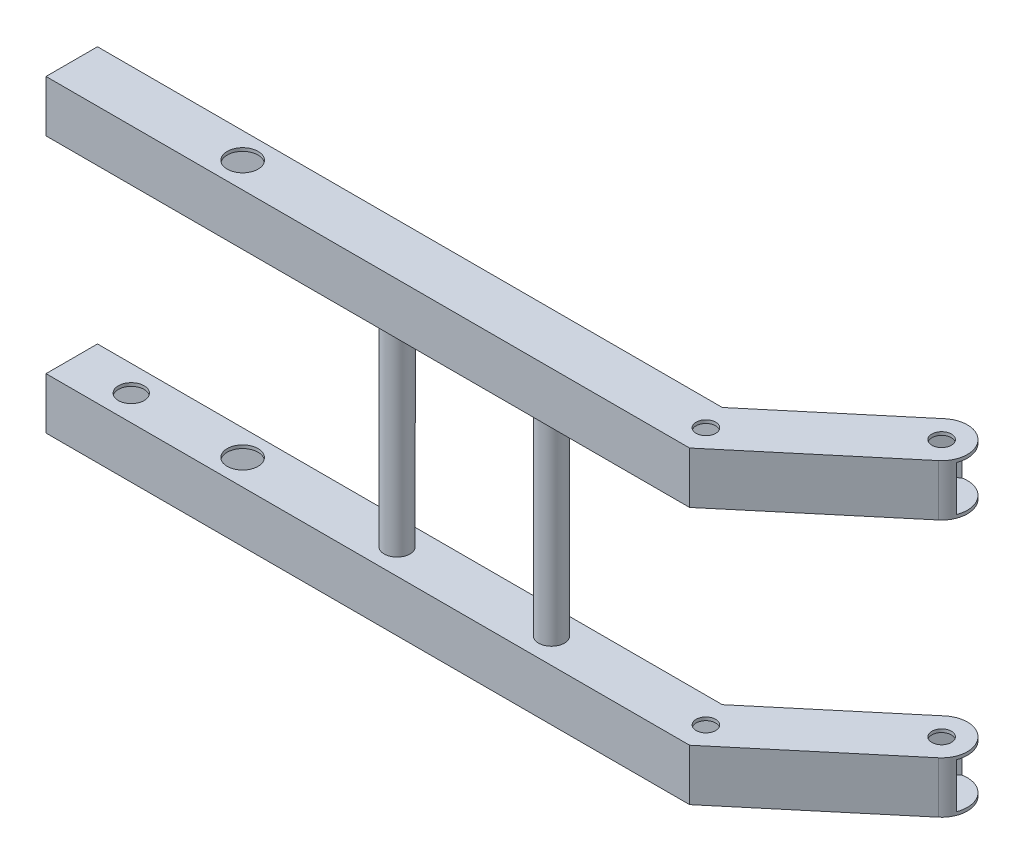
SolidWorks part; units mm, degrees
ref_plane "Front Plane" through (0, 0, 0) normal (0, 0, 1) x (1, 0, 0)
ref_plane "Top Plane" through (0, 0, 0) normal (0, 1, 0) x (1, 0, 0)
ref_plane "Right Plane" through (0, 0, 0) normal (1, 0, 0) x (0, 0, -1)
sketch "Sketch4" plane through (0, 0, 0) normal (0, 1, 0) x (1, 0, 0)
  line L0 (0, 0) -> (-254, 0) construction
  line L1 (0, 0) -> (91.1351, 76.4714) construction
  line L2 (-254, -12.7) -> (-254, 12.7)
  line L3 (4.6224, -12.7) -> (-4.6224, 12.7) construction
  line L4 (-254, 12.7) -> (-4.6224, 12.7)
  line L5 (99.2985, 66.7427) -> (82.9717, 86.2002)
  line L6 (82.9717, 86.2002) -> (-4.6224, 12.7)
  line L7 (-254, -12.7) -> (4.6224, -12.7)
  line L8 (4.6224, -12.7) -> (99.2985, 66.7427)
  circle A0 centre (0, 0) radius 4.826
  circle A1 centre (63.237, 53.0621) radius 4.826
  circle A3 centre (-228.6, 0) radius 7.62
  point P7 (-254, 0)
  point P10 (0, 0)
  point P13 (91.1351, 76.4714)
  dimension "D2" = 9.652
  dimension "D7" = 15.24
  dimension "D1" = 82.55
  dimension "D3" = 25.4
  dimension "D5" = 25.4
  dimension "D6" = 228.6
extrude "Boss-Extrude3" add sketch "Sketch4" along normal blind 152.4
sketch "Sketch5" plane through (-254, 0, 0) normal (-1, 0, 0) x (0, 0, 1)
  line L0 (0, 152.4) -> (0, 0) construction
  line L3 (-12.7, 152.4) -> (12.7, 152.4) construction
  line L6 (-12.7, 0) -> (12.7, 0) construction
  line L7 (11.1125, 128.5875) -> (-11.1125, 128.5875)
  line L8 (11.1125, 128.5875) -> (11.1125, 150.8125)
  line L9 (11.1125, 150.8125) -> (-11.1125, 150.8125)
  line L10 (-11.1125, 128.5875) -> (-11.1125, 150.8125)
  line L11 (11.1125, 128.5875) -> (-11.1125, 150.8125) construction
  line L12 (11.1125, 150.8125) -> (-11.1125, 128.5875) construction
  line L13 (-12.7, 127) -> (12.7, 127)
  line L14 (-12.7, 152.4) -> (-12.7, 0) construction
  line L15 (12.7, 152.4) -> (12.7, 0) construction
  line L16 (11.1125, 1.5875) -> (-11.1125, 1.5875)
  line L17 (11.1125, 1.5875) -> (11.1125, 23.8125)
  line L18 (11.1125, 23.8125) -> (-11.1125, 23.8125)
  line L19 (-11.1125, 1.5875) -> (-11.1125, 23.8125)
  line L20 (11.1125, 1.5875) -> (-11.1125, 23.8125) construction
  line L21 (11.1125, 23.8125) -> (-11.1125, 1.5875) construction
  line L22 (-12.7, 25.4) -> (12.7, 25.4)
  line L23 (-12.7, 25.4) -> (-12.7, 127)
  line L24 (12.7, 127) -> (12.7, 25.4)
  point P12 (0, 139.7)
  point P19 (0, 12.7)
  point P24 (0, 0)
  point P26 (0, 25.4)
  dimension "D1" = 1.5875
  dimension "D2" = 12.7
  dimension "D3" = 12.7
  dimension "D4" = 1.5875
  dimension "D5" = 12.7
  dimension "D6" = 12.7
extrude "Cut-Extrude2" cut sketch "Sketch5" against normal up to vertex (258.6224 mm away) up to point (4.6224, 152.4, 12.7)
sketch "Sketch6" plane through (91.1351, 0, -76.4714) normal (0.766, 0, -0.6428) x (-0.6428, 0, -0.766)
  line L0 (12.7, 127) -> (-12.7, 127)
  line L1 (12.7, 152.4) -> (12.7, 0) construction
  line L3 (0, 0) -> (0, 152.4) construction
  line L4 (-12.7, 0) -> (12.7, 0) construction
  line L5 (-12.7, 152.4) -> (12.7, 152.4) construction
  line L6 (-12.7, 152.4) -> (-12.7, 0) construction
  line L7 (-11.1125, 128.5875) -> (11.1125, 128.5875)
  line L8 (-11.1125, 128.5875) -> (-11.1125, 150.8125)
  line L9 (-11.1125, 150.8125) -> (11.1125, 150.8125)
  line L10 (11.1125, 128.5875) -> (11.1125, 150.8125)
  line L11 (-11.1125, 128.5875) -> (11.1125, 150.8125) construction
  line L12 (-11.1125, 150.8125) -> (11.1125, 128.5875) construction
  line L13 (12.7, 25.4) -> (-12.7, 25.4)
  line L14 (-11.1125, 1.5875) -> (11.1125, 1.5875)
  line L15 (-11.1125, 1.5875) -> (-11.1125, 23.8125)
  line L16 (-11.1125, 23.8125) -> (11.1125, 23.8125)
  line L17 (11.1125, 1.5875) -> (11.1125, 23.8125)
  line L18 (-11.1125, 1.5875) -> (11.1125, 23.8125) construction
  line L19 (-11.1125, 23.8125) -> (11.1125, 1.5875) construction
  line L20 (-12.7, 25.4) -> (-12.7, 127)
  line L21 (12.7, 127) -> (12.7, 25.4)
  point P5 (0, 127)
  point P12 (0, 139.7)
  point P18 (0, 25.4)
  point P19 (0, 12.7)
  point P24 (0, 0)
  dimension "D1" = 1.5875
  dimension "D2" = 12.7
  dimension "D3" = 12.7
  dimension "D4" = 1.5875
  dimension "D5" = 25.4
  dimension "D6" = 12.7
extrude "Cut-Extrude3" cut sketch "Sketch6" against normal up to vertex (123.5909 mm away) up to point (4.6224, 152.4, 12.7)
sketch "Sketch7" plane through (0, 152.4, 0) normal (0, 1, 0) x (1, 0, 0)
  line L0 (71.4004, 43.3334) -> (55.0736, 62.7909) construction
  line L1 (82.9717, 86.2002) -> (-4.6224, 12.7) construction
  line L2 (4.6224, -12.7) -> (99.2985, 66.7427) construction
  line L3 (55.0736, 62.7909) -> (14.2925, 190.3795)
  line L4 (14.2925, 190.3795) -> (153.8443, 116.5917)
  line L5 (153.8443, 116.5917) -> (141.5355, -3.4731)
  line L6 (141.5355, -3.4731) -> (71.4004, 43.3334)
  arc A0 (55.0736, 62.7909) -> (71.4004, 43.3334) centre (63.237, 53.0621) cw
  point P6 (63.237, 53.0621)
  point P7 (63.237, 53.0621)
extrude "Cut-Extrude4" cut sketch "Sketch7" against normal up to surface (152.4 mm away) up to face at (-54.2883, 0, -25.4905)
sketch "Sketch8" plane through (0, 127, 0) normal (0, -1, 0) x (1, 0, 0)
  line L0 (0, 0) -> (-228.6, 0) construction
  circle A0 centre (-76.2, 0) radius 6.35
  circle A1 centre (-152.4, 0) radius 6.35
  dimension "D3" = 12.7
  dimension "D1" = 76.2
  dimension "D2" = 76.2
extrude "Boss-Extrude4" add sketch "Sketch8" along normal up to surface (101.6 mm away) up to face at (-61.9662, 25.4, -19.0479)
sketch "Sketch9" plane through (-254, 0, 0) normal (-1, 0, 0) x (0, 0, 1)
  line L0 (-12.7, 152.4) -> (12.7, 152.4)
  line L1 (12.7, 152.4) -> (12.7, 127)
  line L2 (12.7, 127) -> (-12.7, 127)
  line L3 (-12.7, 152.4) -> (-12.7, 127) construction
  line L4 (12.7, 127) -> (-12.7, 127) construction
  line L5 (-12.7, 127) -> (-12.7, 152.4)
  line L6 (-11.1125, 150.8125) -> (11.1125, 150.8125)
  line L7 (11.1125, 150.8125) -> (11.1125, 128.5875)
  line L8 (11.1125, 128.5875) -> (-11.1125, 128.5875)
  line L9 (-11.1125, 128.5875) -> (-11.1125, 150.8125)
  line L10 (-12.7, 25.4) -> (12.7, 25.4)
  line L11 (12.7, 25.4) -> (12.7, 0)
  line L12 (12.7, 0) -> (-12.7, 0)
  line L13 (-12.7, 0) -> (-12.7, 25.4)
  line L14 (-11.1125, 23.8125) -> (11.1125, 23.8125)
  line L15 (11.1125, 23.8125) -> (11.1125, 1.5875)
  line L16 (11.1125, 1.5875) -> (-11.1125, 1.5875)
  line L17 (-11.1125, 1.5875) -> (-11.1125, 23.8125)
extrude "Boss-Extrude5" add sketch "Sketch9" along normal blind 58.928
sketch "Sketch11" plane through (0, 127, 0) normal (0, -1, 0) x (1, 0, 0)
  line L0 (-312.928, 0) -> (-228.6, 0) construction
  line L1 (-312.928, -12.7) -> (-312.928, 12.7) construction
  circle A0 centre (-271.0548, 0) radius 1.65
  circle A1 centre (-296.0548, 0) radius 1.65
  dimension "D2" = 3.3
  dimension "D1" = 25
extrude "Cut-Extrude6" cut sketch "Sketch11" against normal up to surface (1.5875 mm away) up to face at (0, 128.5875, -4.826)
sketch "Sketch12" plane through (0, 127, 0) normal (0, -1, 0) x (1, 0, 0)
  line L0 (-271.0548, 0) -> (-296.0548, 0) construction
  circle A0 centre (-283.5548, 0) radius 6.35
extrude "Cut-Extrude7" cut sketch "Sketch12" along normal up to surface (103.1875 mm away) up to face at (-228.6, 23.8125, 7.62)
